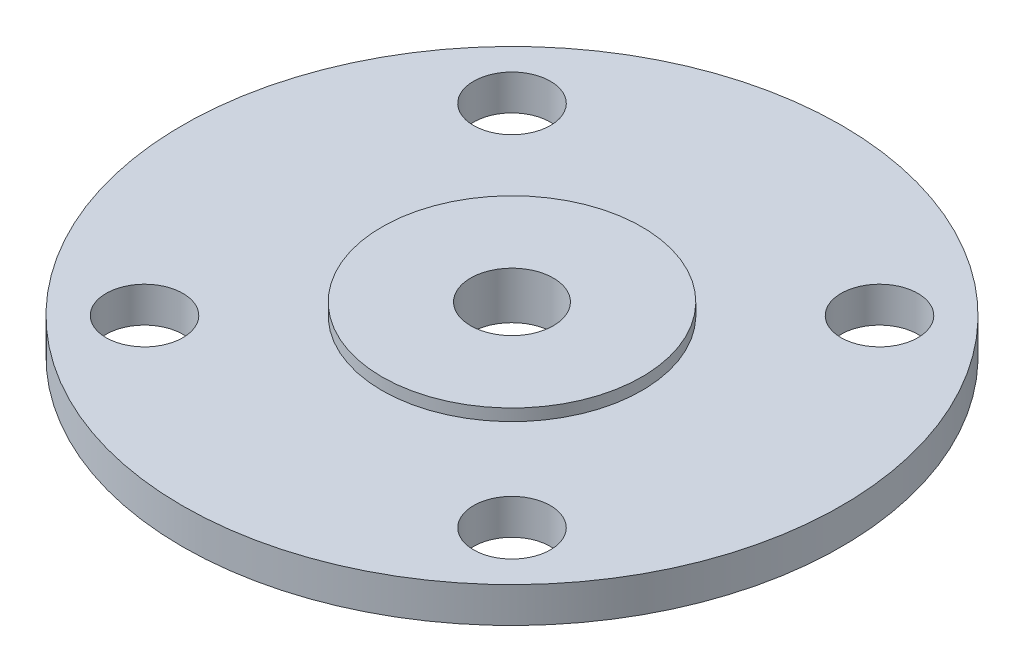
SolidWorks part; units mm, degrees
ref_plane "Front" through (0, 0, 0) normal (0, 0, 1) x (1, 0, 0)
ref_plane "Top" through (0, 0, 0) normal (0, 1, 0) x (1, 0, 0)
ref_plane "Right" through (0, 0, 0) normal (1, 0, 0) x (0, 0, -1)
sketch "Sketch1" plane through (0, 0, 0) normal (0, 1, 0) x (1, 0, 0)
  line L1 (-15.55, -15.55) -> (15.55, -15.55) construction
  line L2 (-15.55, -15.55) -> (-15.55, 15.55) construction
  line L3 (-15.55, 15.55) -> (15.55, 15.55) construction
  line L4 (15.55, -15.55) -> (15.55, 15.55) construction
  line L5 (-15.55, -15.55) -> (15.55, 15.55) construction
  line L6 (-15.55, 15.55) -> (15.55, -15.55) construction
  circle A0 centre (0, 0) radius 3.5
  circle A1 centre (0, 0) radius 11
  circle A2 centre (0, 0) radius 27.8896
  circle A3 centre (15.55, 15.55) radius 3.25
  circle A4 centre (15.55, -15.55) radius 3.25
  circle A5 centre (-15.55, -15.55) radius 3.25
  circle A6 centre (-15.55, 15.55) radius 3.25
  circle A7 centre (0, 0) radius 11 construction
  dimension "D2" = 6.5
  dimension "D3" = 7
  dimension "D1" = 31.1
extrude "Boss-Extrude1" add sketch "Sketch1" against normal blind 3 contours A2 A6 A5 A4 A3 A1 | A1 A0 region at (-10.6889, 0, 0) region at (-27.1008, 0, 0)
extrude "Boss-Extrude2" add sketch "Sketch1<5>" along normal blind 1 contours A1 A0 region at (-10.6889, 0, 0)
sketch "Sketch1<5>" plane through (0, 0, 0) normal (0, 1, 0) x (1, 0, 0) same geometry as "Sketch1"
sketch "Sketch2" plane through (0, -3, 0) normal (0, -1, 0) x (1, 0, 0)
  line L0 (0, 27.8896) -> (0, -27.8896) construction
  line L1 (0, -27.8896) -> (27.8896, 0) construction
  line L2 (27.8896, 0) -> (-27.8896, 0) construction
  line L3 (-27.8896, 0) -> (0, 27.8896) construction
  line L4 (0, 27.8896) -> (27.8896, 0) construction
  line L5 (-27.8896, 0) -> (0, -27.8896) construction
  line L6 (-3, 7.608) -> (-3, 0) construction
  line L7 (-19.608, -3) -> (-7.608, -3)
  line L8 (-19.608, -3) -> (-19.608, 3)
  line L9 (-19.608, 3) -> (-7.608, 3)
  line L11 (-19.608, -3) -> (-7.608, 3) construction
  line L12 (-19.608, 3) -> (-7.608, -3) construction
  line L13 (-3, 19.608) -> (3, 19.608)
  line L14 (-3, 19.608) -> (-3, 7.608)
  line L16 (3, 19.608) -> (3, 7.608)
  line L17 (-3, 19.608) -> (3, 7.608) construction
  line L18 (-3, 7.608) -> (3, 19.608) construction
  line L19 (19.608, -3) -> (7.608, -3)
  line L20 (19.608, -3) -> (19.608, 3)
  line L21 (19.608, 3) -> (7.608, 3)
  line L23 (19.608, -3) -> (7.608, 3) construction
  line L24 (19.608, 3) -> (7.608, -3) construction
  line L25 (-3, -19.608) -> (3, -19.608)
  line L26 (-3, -19.608) -> (-3, -7.608)
  line L28 (3, -19.608) -> (3, -7.608)
  line L29 (-3, -19.608) -> (3, -7.608) construction
  line L30 (-3, -7.608) -> (3, -19.608) construction
  line L31 (-3, 0) -> (-3, -7.608) construction
  line L32 (-7.608, -3) -> (0, -3) construction
  line L33 (0, -3) -> (7.608, -3) construction
  circle A0 centre (0, 0) radius 27.8896 construction
  arc A1 (7.608, -3) -> (7.608, 3) centre (0, 0) ccw
  arc A2 (3, 7.608) -> (-3, 7.608) centre (0, 0) ccw
  arc A3 (-7.608, 3) -> (-7.608, -3) centre (0, 0) ccw
  arc A4 (-3, -7.608) -> (3, -7.608) centre (0, 0) ccw
  point P4 (-13.608, 0)
  point P12 (0, 13.608)
  point P17 (13.608, 0)
  point P22 (0, -13.608)
  dimension "D1" = 12
  dimension "D2" = 6
extrude "Boss-Extrude3" add sketch "Sketch2" along normal blind 6
chamfer "Chamfer1" distance 4 angle 45 4 edges at (-8.1781, -9, 0) (0, -9, 8.1781) (8.1781, -9, 0) (0, -9, -8.1781)
sketch "Sketch3" plane through (-19.608, 0, 0) normal (-1, 0, 0) x (0, 0, 1)
  line L0 (3, -9) -> (3, -3) construction
  line L1 (-3, -9) -> (3, -9) construction
  line L2 (-3, -9) -> (-3, -3) construction
  line L3 (-3, -3) -> (3, -3) construction
  line L4 (3, -9) -> (3, -3) construction
  line L5 (3, -3) -> (-3, -3) construction
  line L6 (-3, -3) -> (3, -9) construction
  line L7 (3, -9) -> (3, -3) construction
  line L8 (3, -3) -> (-3, -9) construction
  circle A0 centre (0, -6) radius 1.5
  dimension "D1" = 3
extrude "Cut-Extrude1" cut sketch "Sketch3" against normal blind 6
pattern_circular "CirPattern1" count 4 over 360 about axis through (0, -3, 0) along (0, 1, 0) of "Cut-Extrude1"
